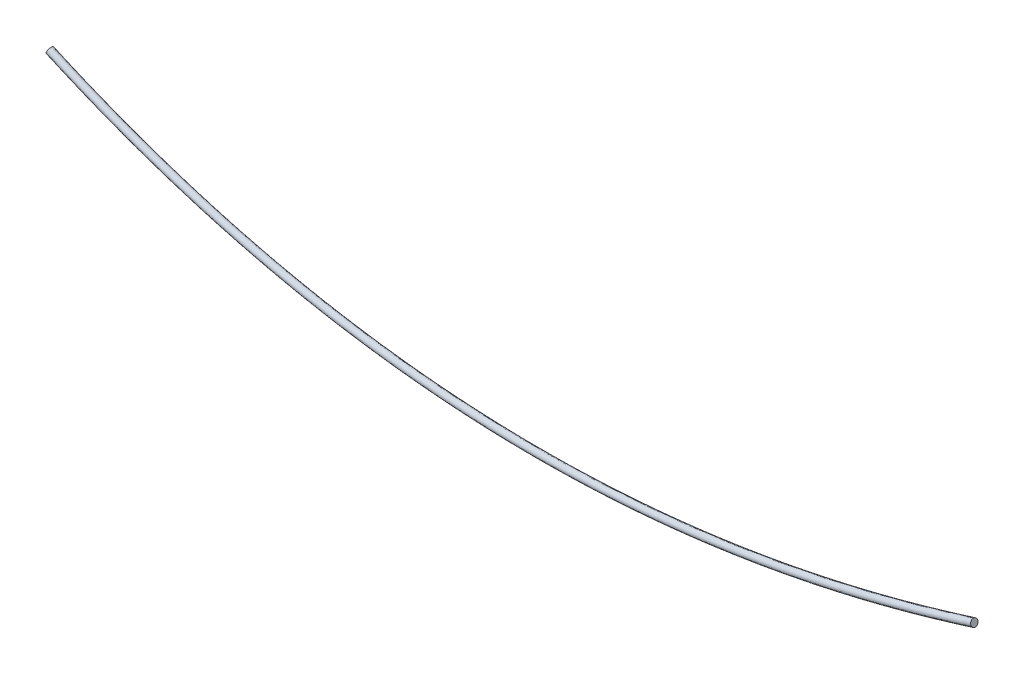
SolidWorks part; units mm, degrees
ref_plane "Front Plane" through (0, 0, 0) normal (0, 0, 1) x (1, 0, 0)
ref_plane "Top Plane" through (0, 0, 0) normal (0, 1, 0) x (1, 0, 0)
ref_plane "Right Plane" through (0, 0, 0) normal (1, 0, 0) x (0, 0, -1)
sketch "Sketch1" plane through (0, 0, 0) normal (0, 0, 1) x (1, 0, 0)
  spline S0 degree 2 poles (-593.9259, -278.4655) (7.5757, -548.3771) (708.9614, -325.8855) knots 0 0 0 1 1 1
  point P2 (0, 0)
  point P4 (0, 0)
  point P5 (-512.0123, 192.4356)
  point P6 (-500.7358, -317.0998)
  dimension "D1" = 1303.75
  dimension "D2" = 47.42
sweep "Sweep1" add path "Sketch1" circular profile diameter 10 parameters "D3"=10
